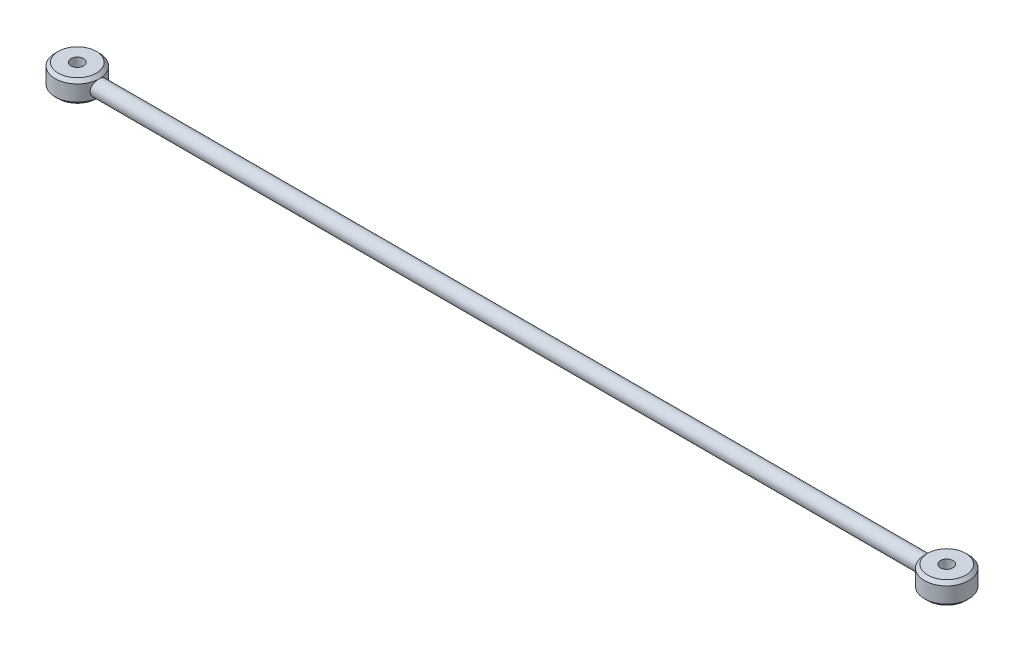
SolidWorks part; units mm, degrees
material "1.5714 (16NiCr4)"
ref_plane "Front Plane" through (0, 0, 0) normal (0, 0, 1) x (1, 0, 0)
ref_plane "Top Plane" through (0, 0, 0) normal (0, 1, 0) x (1, 0, 0)
ref_plane "Right Plane" through (0, 0, 0) normal (1, 0, 0) x (0, 0, -1)
sketch "Sketch1" plane through (0, 0, 0) normal (0, 1, 0) x (1, 0, 0)
  line L0 (0, 0) -> (275, 0) construction
  circle A0 centre (0, 0) radius 7
  circle A1 centre (275, 0) radius 7
  circle A2 centre (0, 0) radius 2
  circle A3 centre (275, 0) radius 2
  dimension "D2" = 4
  dimension "D5" = 14
  dimension "D1" = 275
extrude "Boss-Extrude1" add sketch "Sketch1" along normal blind 3.5 and the other way blind 3.5
ref_plane "Plane1" through (150, 0, 0) normal (1, 0, 0) x (0, 0, -1)
ref_plane "Plane2" through (22.5, 0, 0) normal (1, 0, 0) x (0, 0, -1)
sketch "Sketch2" plane through (22.5, 0, 0) normal (1, 0, 0) x (0, 0, -1)
  circle A0 centre (0, 0) radius 2.5
  dimension "D2" = 5
extrude "Boss-Extrude2" add sketch "Sketch2" along normal up to surface and the other way up to surface up to face at (275, -3.5, 7) other way up to face at (0, -3.5, 7)
chamfer "Chamfer1" distance 1 angle 45 4 edges at (0, -3.5, 7) (0, 3.5, 7) (275, -3.5, 7) (275, 3.5, 7)
